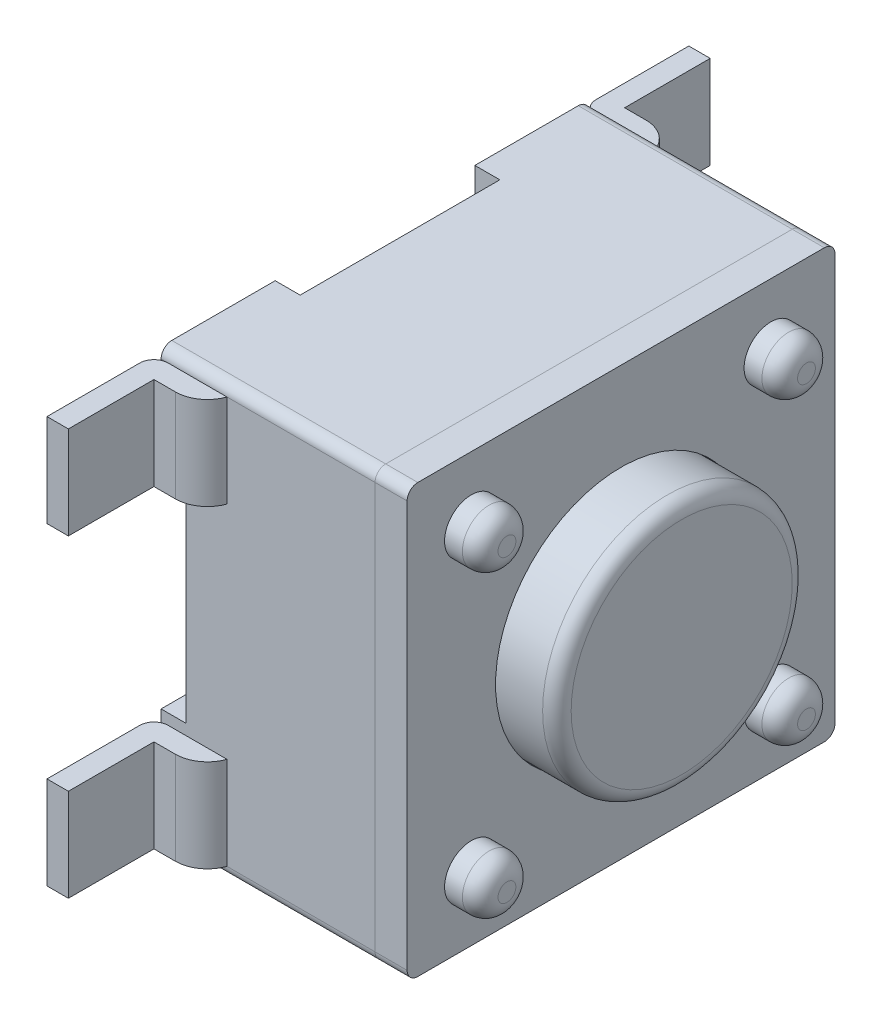
SolidWorks part; units mm, degrees
ref_plane "Front Plane" through (0, 0, 0) normal (0, 0, 1) x (1, 0, 0)
ref_plane "Top Plane" through (0, 0, 0) normal (0, 1, 0) x (1, 0, 0)
ref_plane "Right Plane" through (0, 0, 0) normal (1, 0, 0) x (0, 0, -1)
sketch "Sketch1" plane through (0, 0, 0) normal (1, 0, 0) x (0, 0, -1)
  line L1 (-3, 3) -> (3, 3)
  line L2 (-3, 3) -> (-3, -3)
  line L3 (-3, -3) -> (3, -3)
  line L4 (3, 3) -> (3, -3)
  line L5 (-3, 3) -> (3, -3) construction
  line L6 (-3, -3) -> (3, 3) construction
  point P0 (0, 0)
  dimension "D1" = 6
  dimension "D2" = 6
extrude "Boss-Extrude1" add sketch "Sketch1" along normal mid plane 3
ref_plane "Plane1" through (2.8, 0, 0) normal (-1, 0, 0) x (0, 0, 1)
ref_axis "Axis1" through (3.19, 0, 0) along (-1, 0, 0)
sketch "Sketch3" plane through (1.5, 0, 0) normal (1, 0, 0) x (0, 0, -1)
  circle A0 centre (0, 0) radius 1.75
  dimension "D1" = 3.5
extrude "Boss-Extrude3" add sketch "Sketch3" along normal up to surface (1.3 mm away) up to plane "Plane1"
fillet "Fillet1" radius 0.2 1 edges at (2.8, 0, 1.75)
ref_plane "Plane3" through (1.95, 0, 0) normal (-1, 0, 0) x (0, 0, 1)
sketch "Sketch5" plane through (1.95, 0, 0) normal (-1, 0, 0) x (0, 0, 1)
  line L0 (-2.0504, 0) -> (0, 0) construction
  line L1 (0, 0) -> (0, 1.9131) construction
  line L2 (2.1, 2.1) -> (2.1, 3) construction
  line L3 (2.1, 2.1) -> (3, 2.1) construction
  line L4 (-3, 3) -> (-3, -3)
  line L5 (3, 3) -> (-3, 3)
  line L6 (3, -3) -> (3, 3)
  line L7 (-3, -3) -> (3, -3)
  line L8 (-3, 3) -> (-3, -3)
  line L9 (3, 3) -> (-3, 3)
  line L10 (3, -3) -> (3, 3)
  line L11 (-3, -3) -> (3, -3)
  circle A0 centre (2.1, 2.1) radius 0.375
  circle A1 centre (-2.1, 2.1) radius 0.375
  circle A2 centre (-2.1, -2.1) radius 0.375
  circle A3 centre (2.1, -2.1) radius 0.375
  dimension "D3" = 0.75
  dimension "D2" = 0.9
  dimension "D1" = 0
extrude "Boss-Extrude4" add sketch "Sketch5" along normal up to surface (0.45 mm away) separate body up to face at (1.5, 0, -1.75)
sketch "Sketch6" plane through (1.95, 0, 0) normal (1, 0, 0) x (0, 0, -1)
  line L4 (3, -3) -> (3, 3)
  line L5 (-3, -3) -> (3, -3)
  line L6 (-3, 3) -> (-3, -3)
  line L7 (3, 3) -> (-3, 3)
  line L8 (3, -3) -> (3, 3) construction
  line L9 (-3, -3) -> (3, -3) construction
  line L10 (-3, 3) -> (-3, -3) construction
  line L11 (3, 3) -> (-3, 3) construction
  circle A1 centre (-2.1, -2.1) radius 0.375
  circle A2 centre (-2.1, -2.1) radius 0.375
  circle A3 centre (2.1, -2.1) radius 0.375
  circle A4 centre (2.1, -2.1) radius 0.375
  circle A5 centre (2.1, 2.1) radius 0.375
  circle A6 centre (2.1, 2.1) radius 0.375
  circle A7 centre (-2.1, 2.1) radius 0.375
  circle A8 centre (-2.1, 2.1) radius 0.375
  dimension "D1" = 0
  dimension "D2" = 0
  dimension "D3" = 0
  dimension "D4" = 0
  dimension "D5" = 0
extrude "Boss-Extrude5" add sketch "Sketch6" along normal blind 0.5 and the other way up to body separate body
fillet "Fillet2" radius 0.25 4 edges at (2.45, -2.1, -2.475) (2.45, 2.1, -2.475) (2.45, 2.1, 1.725) (2.45, -2.1, 1.725)
fillet "Fillet3" radius 0.15 4 edges at (0, 3, 3) (0, 3, -3) (0, -3, 3) (0, -3, -3)
fillet "Fillet4" radius 0.15 4 edges at (1.725, 3, 3) (1.725, -3, 3) (1.725, -3, -3) (1.725, 3, -3)
ref_plane "Plane4" through (0, -2.2, 0) normal (0, 1, 0) x (1, 0, 0)
sketch "Sketch7" plane through (0, -2.2, 0) normal (0, 1, 0) x (1, 0, 0)
  line L0 (-1, -3) -> (-1.4, -3)
  line L4 (-1.5, -2.85) -> (-1.5, 2.85) construction
  line L5 (-1, -3.3) -> (-1.3, -3.3)
  line L10 (-1, -3) -> (-0.5757, -3)
  line L11 (1.5, -3) -> (-1.5, -3) construction
  line L12 (0, 0) -> (-3.3, 0) construction
  line L13 (-1.5196, -3.3) -> (-2.9964, -4.1526) construction
  line L14 (-2.9964, -4.1526) -> (-4.3, -3.4) construction
  line L15 (-1.6, -3) -> (-2.9964, -3.8062) construction
  line L16 (-4.3, -3.4) -> (-5, -3.4) construction
  line L17 (-2.9964, -3.8062) -> (-4.2196, -3.1) construction
  line L18 (-4.2196, -3.1) -> (-5, -3.1) construction
  line L19 (-1.6, -3.2) -> (-1.6, -4.5)
  line L20 (-1.6, -4.5) -> (-1.3, -4.5)
  line L21 (-1.3, -4.5) -> (-1.3, -3.3)
  line L22 (-1, 3) -> (-0.5757, 3)
  line L23 (-1, -3.3) -> (-1.5196, -3.3) construction
  line L24 (-1, 3) -> (-1.4, 3)
  line L25 (-1.6, 3.2) -> (-1.6, 4.5)
  line L26 (-1.6, 4.5) -> (-1.3, 4.5)
  line L27 (-1.3, 4.5) -> (-1.3, 3.3)
  line L28 (-1, 3.3) -> (-1.3, 3.3)
  line L29 (-1, -3) -> (-1.6, -3) construction
  arc A0 (-1, -3.3) -> (-0.5757, -3) centre (-1, -2.85) ccw
  arc A1 (-1, 3.3) -> (-0.5757, 3) centre (-1, 2.85) cw
  arc A2 (-1.6, -3.2) -> (-1.4, -3) centre (-1.4, -3.2) cw
  arc A3 (-1.6, 3.2) -> (-1.4, 3) centre (-1.4, 3.2) ccw
  dimension "D5" = 0.45
  dimension "D7" = 0.2
  dimension "D8" = 0.2
  dimension "D1" = 0.3
  dimension "D2" = 4.5
  dimension "D4" = 0.1
  dimension "D6" = 1
  dimension "D9" = 1.3
  dimension "D3" = 0.3
extrude "Boss-Extrude6" add sketch "Sketch7" along normal mid plane 1.3 separate body
mirror "Mirror3" about plane through (0, 0, 0) normal (0, 1, 0) of bodies 112
mirror "Mirror5" about plane through (0, 0, 0) normal (0, 0, 1) of bodies 113 115
sketch "Sketch9" plane through (0, 3, 0) normal (0, 1, 0) x (1, 0, 0)
  line L0 (-1.5, 2.85) -> (-1.5, -2.85) construction
  line L1 (-1.85, 1.4) -> (-1.15, 1.4)
  line L2 (-1.85, 1.4) -> (-1.85, -1.4)
  line L3 (-1.85, -1.4) -> (-1.15, -1.4)
  line L4 (-1.15, 1.4) -> (-1.15, -1.4)
  line L5 (-1.85, 1.4) -> (-1.15, -1.4) construction
  line L6 (-1.85, -1.4) -> (-1.15, 1.4) construction
  point P0 (-1.5, 0)
  dimension "D1" = 2.8
  dimension "D2" = 0.35
extrude "Cut-Extrude3" cut sketch "Sketch9" against normal through all
pattern_circular "CirPattern2" count 4 over 360 about axis through (3.19, 0, 0) along (-1, 0, 0) of "Cut-Extrude3"
sketch "Sketch11" plane through (1.95, 0, 0) normal (1, 0, 0) x (0, 0, -1)
  circle A0 centre (0, 0) radius 1.76
  circle A1 centre (0, 0) radius 1.75
  circle A2 centre (0, 0) radius 1.75 construction
  dimension "D1" = 0
  dimension "D2" = 0.01
extrude "Cut-Extrude5" cut sketch "Sketch11" against normal up to next (0.45 mm away)
sketch "Sketch10" plane through (1.95, 0, 0) normal (1, 0, 0) x (0, 0, -1)
  line L0 (-3, -2.85) -> (-3, 2.85) construction
  line L1 (-3.2, 0.75) -> (-2.8, 0.75)
  line L2 (-3.2, 0.75) -> (-3.2, -0.75)
  line L3 (-3.2, -0.75) -> (-2.8, -0.75)
  line L4 (-2.8, 0.75) -> (-2.8, -0.75)
  line L5 (-3.2, 0.75) -> (-2.8, -0.75) construction
  line L6 (-3.2, -0.75) -> (-2.8, 0.75) construction
  point P0 (-3, 0)
  dimension "D1" = 1.5
  dimension "D2" = 0.2
extrude "Cut-Extrude4" [suppressed] cut sketch "Sketch10" against normal up to next
pattern_circular "CirPattern1" [suppressed] count 4 over 360 about axis through (3.19, 0, 0) along (-1, 0, 0) of bodies 119
